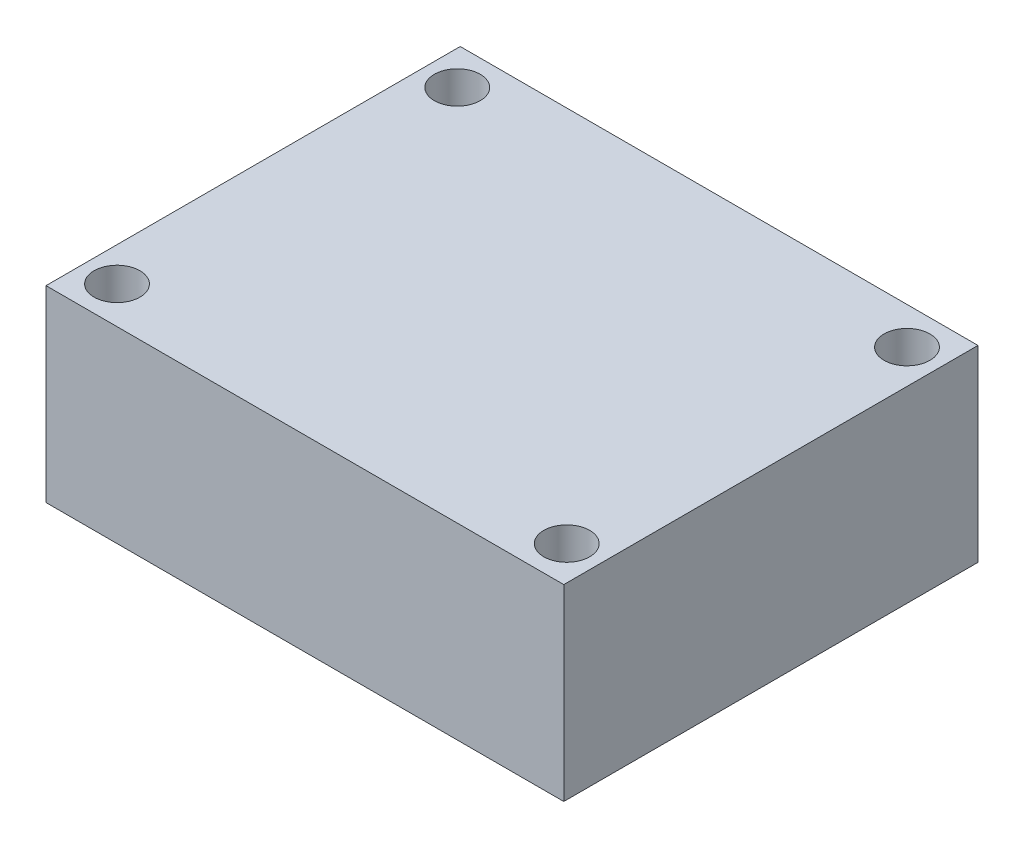
SolidWorks part; units mm, degrees
material "ABS"
ref_plane "Front Plane" through (0, 0, 0) normal (0, 0, 1) x (1, 0, 0)
ref_plane "Top Plane" through (0, 0, 0) normal (0, 1, 0) x (1, 0, 0)
ref_plane "Right Plane" through (0, 0, 0) normal (1, 0, 0) x (0, 0, -1)
sketch "Sketch1" plane through (0, 0, 0) normal (0, 1, 0) x (1, 0, 0)
  line L0 (0, 0) -> (0, 5.7699) construction
  line L1 (-17.5, 14) -> (17.5, 14)
  line L2 (-17.5, 14) -> (-17.5, -14)
  line L3 (-17.5, -14) -> (17.5, -14)
  line L4 (17.5, 14) -> (17.5, -14)
  line L5 (-17.5, 14) -> (17.5, -14) construction
  line L6 (-17.5, -14) -> (17.5, 14) construction
  line L7 (0, 0) -> (-7.7865, 0) construction
  circle A0 centre (-15.2, 11.5) radius 1.55
  circle A1 centre (15.2, 11.5) radius 1.55
  circle A2 centre (-15.2, -11.5) radius 1.55
  circle A3 centre (15.2, -11.5) radius 1.55
  point P0 (0, 0)
  dimension "D3" = 3.1
  dimension "D4" = 2.5
  dimension "D5" = 2.3
  dimension "D1" = 35
  dimension "D2" = 28
extrude "Boss-Extrude1" add sketch "Sketch1" along normal blind 12.7
